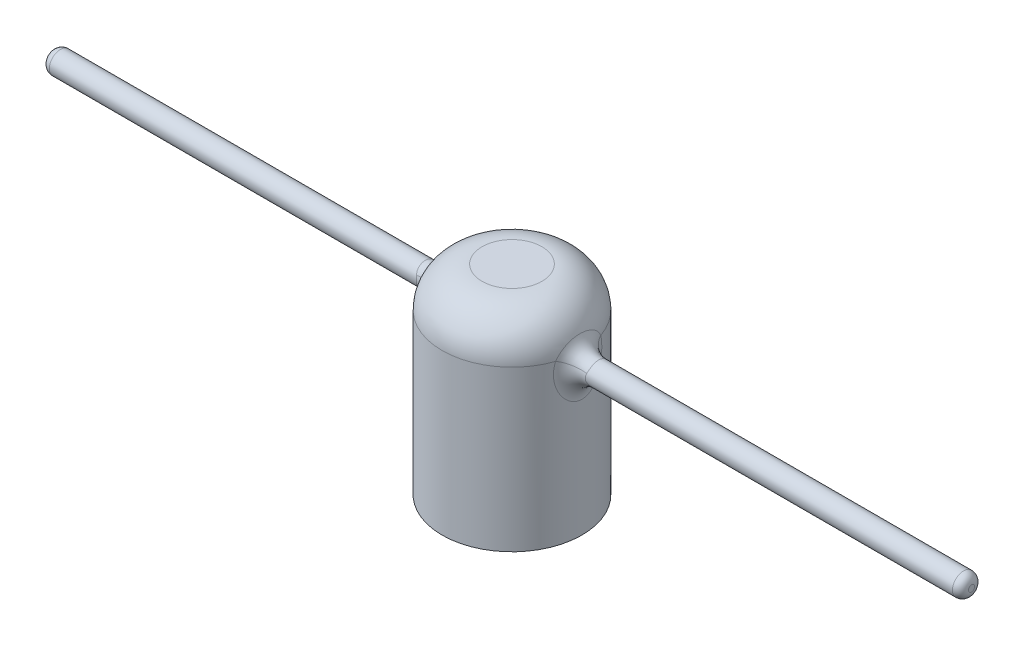
SolidWorks part; units mm, degrees
material "Alloy Steel"
ref_plane "Front Plane" through (0, 0, 0) normal (0, 0, 1) x (1, 0, 0)
ref_plane "Top Plane" through (0, 0, 0) normal (0, 1, 0) x (1, 0, 0)
ref_plane "Right Plane" through (0, 0, 0) normal (1, 0, 0) x (0, 0, -1)
sketch "Sketch1" plane through (0, 0, 0) normal (0, 1, 0) x (1, 0, 0)
  circle A0 centre (0, 0) radius 17.5
  dimension "D1" = 35
extrude "Boss-Extrude1" add sketch "Sketch1" along normal blind 50
fillet "Fillet1" radius 10 1 edges at (0, 50, 17.5)
sketch "Sketch2" plane through (0, 0, 0) normal (1, 0, 0) x (0, 0, -1)
  line L0 (0, 19.25) -> (0, -19.25) construction
  line L1 (-17.5, 40) -> (17.5, 40) construction
  circle A0 centre (0, 37.2192) radius 2.7808
  dimension "D1" = 5.5616
extrude "Boss-Extrude3" add sketch "Sketch2" along normal mid plane 230 contours A0
fillet "Fillet2" radius 2 2 edges at (115, 37.2192, -2.7808) (-115, 37.2192, -2.7808)
fillet "Fillet3" radius 5 2 edges at (17.4889, 34.5095, 0.6244) (-17.4775, 34.584, 0.8878)
sketch "Sketch3" plane through (0, 0, 0) normal (0, -1, 0) x (1, 0, 0)
  point P0 (0, 0)
  point P1 (-60.2925, 11.6092)
hole_wizard "M16 Tapped Hole2" positions "Sketch5" profile "Sketch6" tap size "M16" standard "ISO"
sketch "Sketch5" plane through (0, 0, 0) normal (0, -1, 0) x (-1, 0, 0)
  point P0 (0, 0)
sketch "Sketch6" plane through (0, 0, 0) normal (1, 0, 0) x (0, 0, -1)
  line L0 (0, 0) -> (0, 45)
  line L1 (0, 45) -> (7, 38)
  line L2 (7, 38) -> (7, 0)
  line L5 (7, 0) -> (0, 0)
  line L10 (0, 45) -> (-7, 38) construction
  line L11 (0, -6.35) -> (0, 107.95) construction
  dimension "Tap Drill Dia." = 14
  dimension "Tap Drill Depth" = 38
  dimension "Drill Angle" = 90
cosmetic thread "Hole Thread4" parameters "D1"=32, "D2"=16
